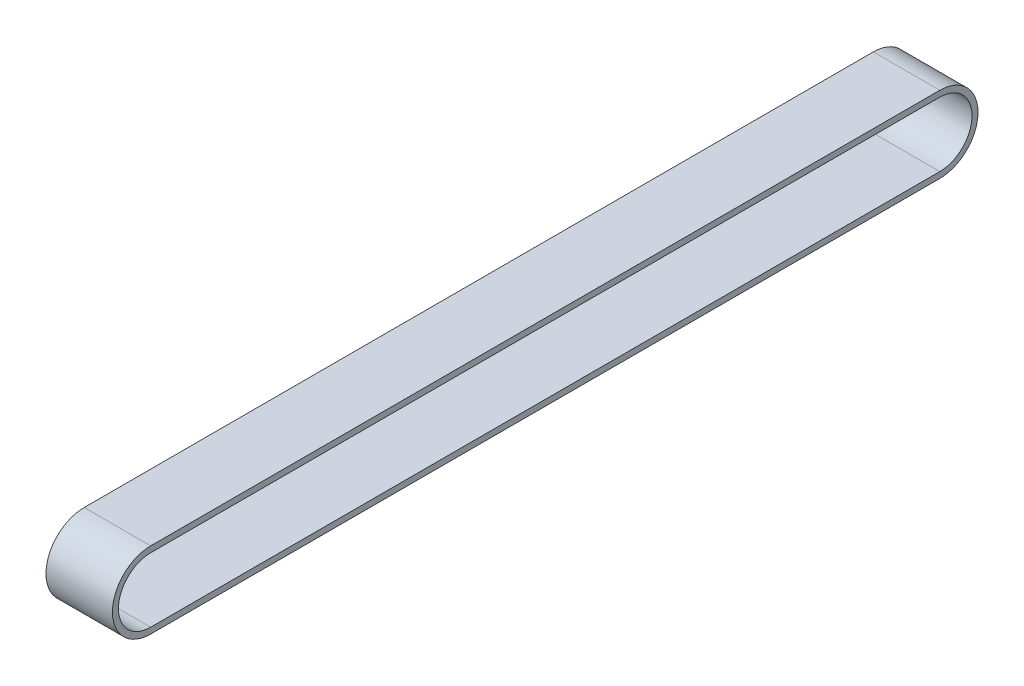
SolidWorks part; units mm, degrees
material "PUR"
ref_plane "Front" through (0, 0, 0) normal (0, 0, 1) x (1, 0, 0)
ref_plane "Top" through (0, 0, 0) normal (0, 1, 0) x (1, 0, 0)
ref_plane "Right" through (0, 0, 0) normal (1, 0, 0) x (0, 0, -1)
sketch "Sketch1" plane through (0, 0, 0) normal (1, 0, 0) x (0, 0, -1)
  line L0 (-150.8125, 0) -> (150.8125, 0) construction
  line L1 (-150.8125, 14.605) -> (150.8125, 14.605)
  line L2 (-150.8125, -14.605) -> (150.8125, -14.605)
  line L3 (-150.8125, 0) -> (150.8125, 0) construction
  line L4 (-150.8125, 12.319) -> (150.8125, 12.319)
  line L5 (-150.8125, -12.319) -> (150.8125, -12.319)
  arc A0 (-150.8125, 14.605) -> (-150.8125, -14.605) centre (-150.8125, 0) ccw
  arc A1 (150.8125, -14.605) -> (150.8125, 14.605) centre (150.8125, 0) ccw
  arc A2 (-150.8125, 12.319) -> (-150.8125, -12.319) centre (-150.8125, 0) ccw
  arc A3 (150.8125, -12.319) -> (150.8125, 12.319) centre (150.8125, 0) ccw
  point P2 (0, 0)
  point P9 (0, 0)
  dimension "D2" = 24.638
  dimension "D1" = 2.286
  dimension "D3" = 301.625
extrude "Boss-Extrude1" add sketch "Sketch1" along normal mid plane 25.4
